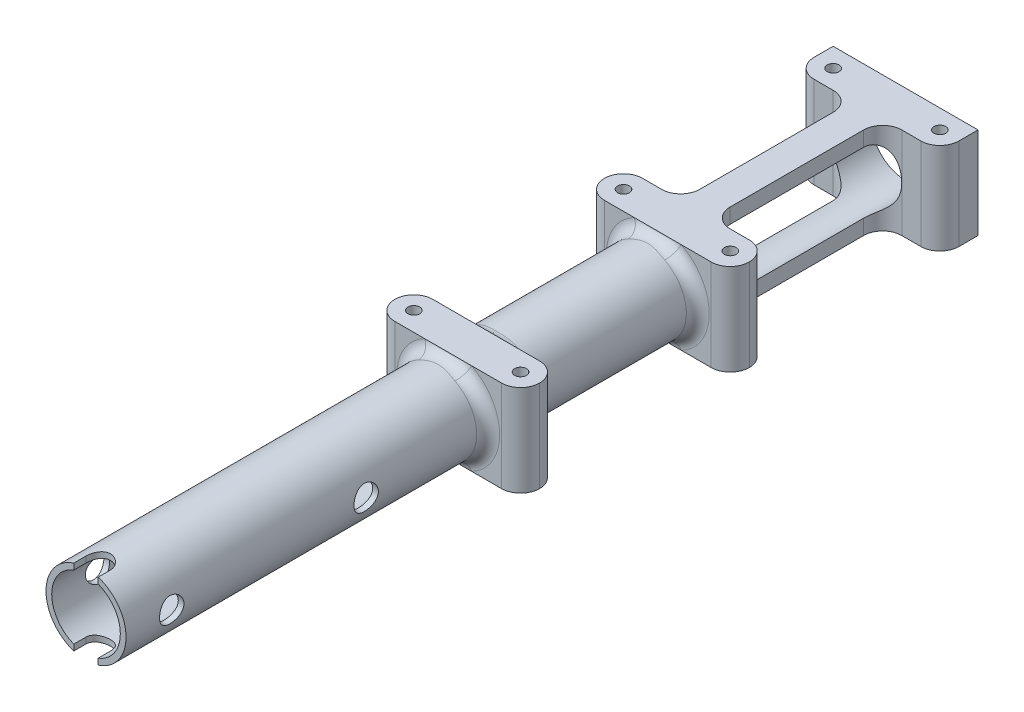
SolidWorks part; units mm, degrees
material "6063-T6"
ref_plane "Front Plane" through (0, 0, 0) normal (0, 0, 1) x (1, 0, 0)
ref_plane "Top Plane" through (0, 0, 0) normal (0, 1, 0) x (1, 0, 0)
ref_plane "Right Plane" through (0, 0, 0) normal (1, 0, 0) x (0, 0, -1)
sketch "Sketch1" plane through (0, 0, 0) normal (0, 0, 1) x (1, 0, 0)
  circle A1 centre (0, 0) radius 10.5
  dimension "D1" = 21
extrude "Boss-Extrude1" add sketch "Sketch1" along normal blind 150
sketch "Sketch3" plane through (0, 0, 0) normal (0, 1, 0) x (1, 0, 0)
  line L0 (0, 0) -> (0, 101.6874) construction
  line L2 (19, 0) -> (-19, 0)
  line L3 (-19, 0) -> (-19, 10)
  line L4 (-19, 10) -> (-4, 10)
  line L5 (-4, 10) -> (-4, 55)
  line L6 (-4, 55) -> (-19, 55)
  line L7 (-19, 55) -> (-19, 65)
  line L8 (-19, 65) -> (19, 65)
  line L9 (19, 55) -> (19, 65)
  line L10 (4, 55) -> (19, 55)
  line L11 (4, 10) -> (4, 55)
  line L12 (19, 10) -> (4, 10)
  line L13 (19, 0) -> (19, 10)
  line L14 (-19, 5) -> (35.7917, 5) construction
  line L15 (-19, 60) -> (20.8388, 60) construction
  line L16 (14, -50) -> (-14, -50) construction
  line L24 (0, -50) -> (0, 0) construction
  line L28 (-19, -55) -> (19, -55)
  line L29 (-19, -55) -> (-19, -45)
  line L30 (-19, -45) -> (19, -45)
  line L31 (19, -55) -> (19, -45)
  line L32 (-19, -55) -> (19, -45) construction
  line L33 (-19, -45) -> (19, -55) construction
  circle A0 centre (-14, 5) radius 1.55
  circle A1 centre (14, 5) radius 1.55
  circle A4 centre (-14, 60) radius 1.55
  circle A5 centre (14, 60) radius 1.55
  circle A6 centre (14, -50) radius 1.55
  circle A7 centre (-14, -50) radius 1.55
  point P12 (0, 65)
  point P29 (0, 0)
  point P30 (0, 2.1375)
  point P31 (0, 0)
  point P32 (0, 0)
  point P33 (-63.2483, 0)
  point P44 (0, 0)
  point P45 (0, -50)
  point P46 (0, 0)
  point P47 (0, 0)
  point P48 (0, -50)
  point P49 (-20, -55)
  point P50 (5.137, -47.4153)
  dimension "D6" = 3.1
  dimension "D8" = 3.1
  dimension "D11" = 28
  dimension "D12" = 55
  dimension "D13" = 28
  dimension "D7" = 28
  dimension "D2" = 45
  dimension "D3" = 10
  dimension "D4" = 10
  dimension "D5" = 8
  dimension "D10" = 38
  dimension "D14" = 38
  dimension "D16" = 10
  dimension "D17" = 38
extrude "Boss-Extrude2" add sketch "Sketch3" along normal blind 12 and the other way blind 12
sketch "Sketch6" plane through (0, 0, 0) normal (0, 0, 1) x (1, 0, 0)
  circle A0 centre (0, 0) radius 9
  dimension "D1" = 18
extrude "Cut-Extrude1" cut sketch "Sketch6" against normal through all both and the other way through all
sketch "Sketch7" plane through (0, 0, 0) normal (1, 0, 0) x (0, 0, -1)
  line L0 (-150, 9) -> (-150, -9) construction
  line L1 (-138, 0) -> (0, 0) construction
  circle A0 centre (-87, 0) radius 3.2
  circle A1 centre (-138, 0) radius 3.2
  point P6 (0, 0)
  point P9 (-87, 0)
  dimension "D1" = 6.4
  dimension "D2" = 12
  dimension "D3" = 63
extrude "Cut-Extrude2" cut sketch "Sketch7" against normal through all both and the other way through all
sketch "Sketch8" plane through (0, 0, 0) normal (0, 1, 0) x (1, 0, 0)
  line L0 (0, 0) -> (0, -186.8535) construction
  line L1 (3.2, -150) -> (-3.2, -150)
  line L2 (-3.2, -150) -> (-3.2, -146.8)
  line L3 (3.2, -150) -> (3.2, -146.8)
  line L4 (-10.5, -150) -> (10.5, -150) construction
  line L5 (-3.2, -146.8) -> (3.2, -146.8) construction
  arc A0 (-3.2, -146.8) -> (3.2, -146.8) centre (0, -146.8) cw
  point P9 (0, -150)
  point P11 (0, -146.8)
  point P12 (0, 0)
  dimension "D1" = 3.2
  dimension "D2" = 3.2
extrude "Cut-Extrude3" cut sketch "Sketch8" along normal up to next and the other way up to next
fillet "Fillet1" radius 5 18 edges at (-4, 10.0311, -55) (4, 10.0311, -55) (-4, 10.0311, -10) (4, 10.0311, -10) (-4, -10.0311, -55) (4, -10.0311, -55) (4, -10.0311, -10) (-4, -10.0311, -10) (-19, 0, -10) (-19, 0, 0) (-19, 0, -55) (19, 0, -55) (19, 0, -10) (19, 0, 0) (-19, 0, 45) (-19, 0, 55) (19, 0, 55) (19, 0, 45)
fillet "Fillet3" radius 3 3 edges at (10.5, 0, 0) (-10.5, 0, 45) (10.5, 0, 55)
